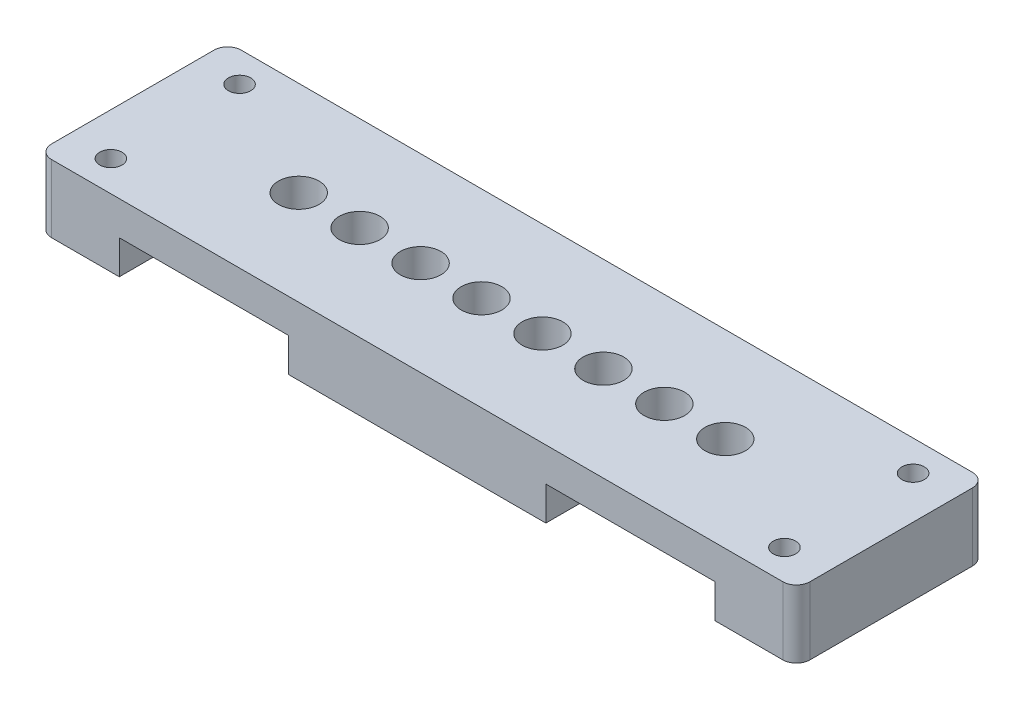
SolidWorks part; units mm, degrees
ref_plane "Front Plane" through (0, 0, 0) normal (0, 0, 1) x (1, 0, 0)
ref_plane "Top Plane" through (0, 0, 0) normal (0, 1, 0) x (1, 0, 0)
ref_plane "Right Plane" through (0, 0, 0) normal (1, 0, 0) x (0, 0, -1)
sketch "Sketch1" plane through (0, 0, 0) normal (0, 0, 1) x (1, 0, 0)
  line L8 (-56, 10) -> (-56, 0)
  line L9 (-56, 0) -> (0, 0)
  line L10 (0, -1055) -> (0, 0) construction
  line L12 (-56, 10) -> (0, 10)
  line L13 (0, 0) -> (0, 72.4167) construction
  line L14 (0, 10) -> (0, 0)
  dimension "D1" = 10
  dimension "D4" = 112
extrude "Boss-Extrude1" add sketch "Sketch1" along normal mid plane 28
sketch "Sketch9" plane through (0, 0, 0) normal (0, 1, 0) x (1, 0, 0)
  line L0 (0, 14) -> (-56, 14) construction
  line L1 (-44, 6) -> (-19, 6)
  line L2 (-44, 6) -> (-44, 14)
  line L3 (-44, 14) -> (-19, 14)
  line L4 (-19, 6) -> (-19, 14)
  line L5 (-44, 6) -> (-19, 14) construction
  line L6 (-44, 14) -> (-19, 6) construction
  line L7 (0, -14) -> (-56, -14) construction
  line L8 (-19, -6) -> (-44, -6)
  line L9 (-19, -6) -> (-19, -14)
  line L10 (-19, -14) -> (-44, -14)
  line L11 (-44, -6) -> (-44, -14)
  line L12 (-19, -6) -> (-44, -14) construction
  line L13 (-19, -14) -> (-44, -6) construction
  line L14 (-56, -14) -> (-56, 14) construction
  line L15 (-44, -6) -> (-44, 6) construction
  point P0 (-31.5, 10)
  point P7 (-31.5, -10)
  dimension "D1" = 8
  dimension "D2" = 25
  dimension "D3" = 12
extrude "Cut-Extrude2" cut sketch "Sketch9" along normal blind 5
chamfer "Chamfer2" distance 5 angle 45 2 edges at (-31.5, 5, -6) (-31.5, 5, 6)
sketch "Sketch10" plane through (0, 10, 0) normal (0, 1, 0) x (1, 0, 0)
  line L3 (-4.5, 0) -> (0, 0) construction
  circle A0 centre (-4.5, 0) radius 3
  circle A2 centre (-13.5, 0) radius 3
  circle A3 centre (-22.5, 0) radius 3
  circle A4 centre (-31.5, 0) radius 3
  point P0 (-13.2207, 0)
  dimension "D2" = 6
  dimension "D1" = 4.5
  dimension "D4" = 9
  dimension "D3" = 4
extrude "Cut-Extrude3" cut sketch "Sketch10" against normal through all
mirror "Mirror1" about plane through (0, 10, 14) normal (-1, 0, 0) of bodies 115 109
hole_wizard "Ø3.0mm Dowel Hole1" positions "Sketch6" profile "Sketch7" hole size "Ø3.0" standard "ANSI Metric"
sketch "Sketch6" plane through (0, 10, 0) normal (0, 1, 0) x (1, 0, 0)
  line L1 (-49.74, -9.5) -> (49.74, -9.5) construction
  line L2 (-49.74, -9.5) -> (-49.74, 9.5) construction
  line L3 (-49.74, 9.5) -> (49.74, 9.5) construction
  line L4 (49.74, -9.5) -> (49.74, 9.5) construction
  line L5 (-49.74, -9.5) -> (49.74, 9.5) construction
  line L6 (-49.74, 9.5) -> (49.74, -9.5) construction
  point P4 (49.74, 9.5)
  point P63 (-49.74, -9.5)
  point P64 (-49.74, 9.5)
  point P65 (49.74, -9.5)
  dimension "D1" = 99.48
  dimension "D2" = 19
sketch "Sketch7" plane through (49.74, 10, -9.5) normal (1, 0, 0) x (0, 0, 1)
  line L0 (0, 0) -> (0, 8.9914)
  line L1 (0, 8.9914) -> (1.65, 8)
  line L2 (1.65, 8) -> (1.65, 0)
  line L5 (1.65, 0) -> (0, 0)
  line L10 (0, 8.9914) -> (-1.65, 8) construction
  line L11 (0, -6.35) -> (0, 107.95) construction
  dimension "Hole Dia." = 3.3
  dimension "Hole Depth" = 8
  dimension "Drill Angle" = 118
fillet "Fillet1" radius 2 4 edges at (-56, 5, -14) (-56, 5, 14) (56, 5, -14) (56, 5, 14)
